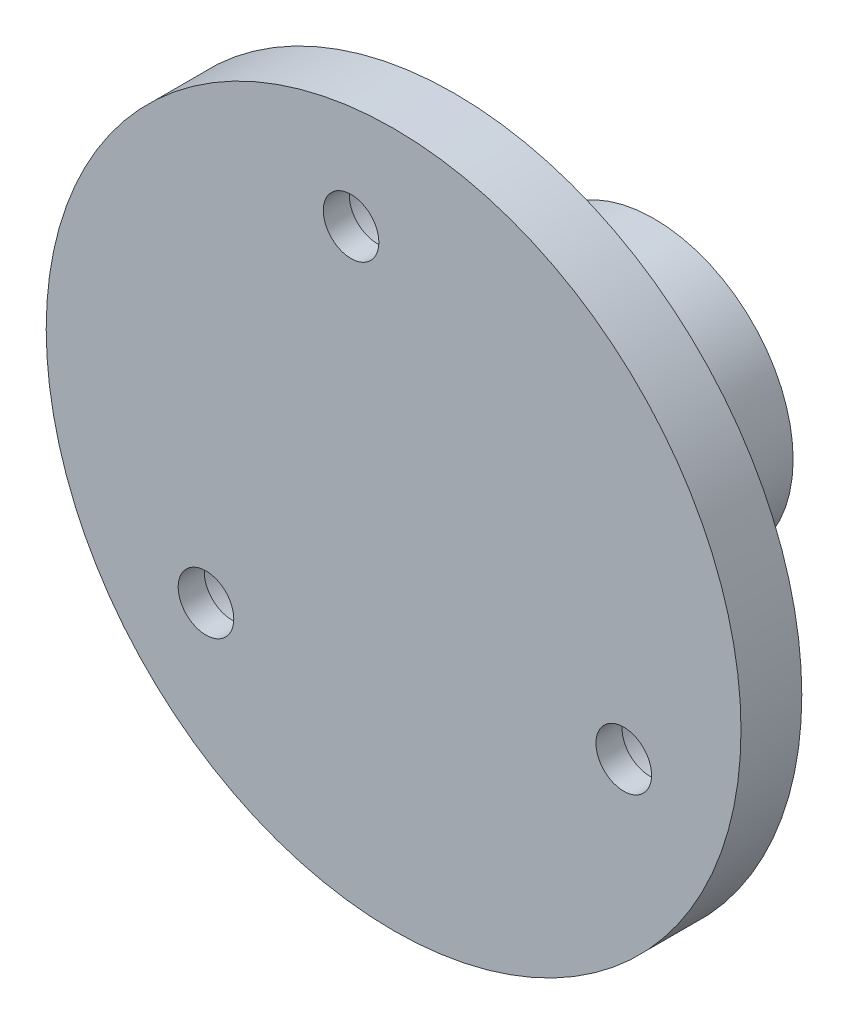
SolidWorks part; units mm, degrees
ref_plane "정면" through (0, 0, 0) normal (0, 0, 1) x (1, 0, 0)
ref_plane "윗면" through (0, 0, 0) normal (0, 1, 0) x (1, 0, 0)
ref_plane "우측면" through (0, 0, 0) normal (1, 0, 0) x (0, 0, -1)
sketch "Sketch1" plane through (0, 0, 0) normal (0, 0, 1) x (1, 0, 0)
  circle A0 centre (0, 0) radius 20
  dimension "D1" = 40
extrude "Boss-Extrude1" add sketch "Sketch1" along normal blind 3.5
sketch "Sketch5" plane through (0, 0, 3.5) normal (0, 0, 1) x (1, 0, 0)
  line L0 (0, 0) -> (-20, 0) construction
  line L1 (0, 0) -> (-10.8012, 9.0633) construction
  line L2 (0, 0) -> (-2.4484, 13.8858) construction
  line L3 (0, 0) -> (0, 15.3364) construction
  circle A0 centre (0, 0) radius 20 construction
  circle A2 centre (-2.4484, 13.8858) radius 1.6
  dimension "D5" = 3.2
  dimension "D1" = 40
  dimension "D2" = 14.1
  dimension "D4" = 40
extrude "Cut-Extrude3" cut sketch "Sketch5" against normal blind 15
sketch "Sketch6" plane through (0, 0, 0) normal (0, 1, 0) x (1, 0, 0)
  line L0 (0, -3.5) -> (0, 2.8067) construction
  line L1 (-20, -3.5) -> (20, -3.5) construction
pattern_circular "CirPattern1" count 3 over 360 about axis through (0, 0, 3.5) along (0, 0, -1) of "Cut-Extrude3" reverse direction yes
sketch "Sketch10" plane through (0, 0, 0) normal (0, 0, -1) x (-1, 0, 0)
  line L0 (0, 0) -> (0, 26.29) construction
  line L2 (-4.6399, 26.3144) -> (0, 0) construction
  circle A0 centre (-1.9101, 10.8329) radius 1.25
  circle A1 centre (-1.9101, 10.8329) radius 2.25
  dimension "D5" = 2.5
  dimension "D6" = 4.5
  dimension "D1" = 26.29
  dimension "D2" = 4.64
  dimension "D3" = 10
  dimension "D4" = 11
sketch "Sketch11" plane through (0, 0, 0) normal (0, 0, -1) x (-1, 0, 0)
  line L1 (3.1173, -2.5064) -> (1.9929, 3.4682)
  circle A0 centre (0, 0) radius 8
  arc A1 (1.9929, 3.4682) -> (3.1173, -2.5064) centre (0, 0) ccw
  dimension "D1" = 16
  dimension "D2" = 8
  dimension "D3" = 2.6
extrude "Boss-Extrude2" add sketch "Sketch11" along normal blind 11.5
ref_plane "Plane1" through (0, 0, 0) normal (0.9848, -0.1736, 0) x (0, 0, -1)
ref_plane "Plane2" through (0, 0, 0) normal (-0.1736, -0.9848, 0) x (0, 0, -1)
sketch "Sketch13" plane through (0, 0, 0) normal (0, 0, -1) x (-1, 0, 0)
  line L0 (-7.643, -2.3631) -> (7.9903, 0.3935)
  line L1 (-3.416, -0.6023) -> (3.416, 0.6023) construction
  arc A0 (-7.643, -2.3631) -> (7.9903, 0.3935) centre (0, 0) ccw
  circle A1 centre (0, 0) radius 8 construction
  dimension "D1" = 1
extrude "Cut-Extrude4" cut sketch "Sketch13" along normal blind 1.5
sketch "Sketch14" plane through (0, 0, 0) normal (0.9848, -0.1736, 0) x (0, 0, -1)
  line L0 (1.5, -1) -> (0, -1) construction
  line L1 (2, -1) -> (11.5, -1)
  line L2 (2, -1) -> (2, -24.9186)
  line L3 (2, -24.9186) -> (11.5, -24.9186)
  line L4 (11.5, -1) -> (11.5, -24.9186)
  line L5 (11.5, -8) -> (11.5, 8) construction
extrude "Cut-Extrude5" cut sketch "Sketch14" against normal blind 1 and the other way blind 1
sketch "Sketch15" plane through (-0.9848, 0.1736, 0) normal (0.9848, -0.1736, 0) x (0, 0, -1)
  line L0 (11.5, -7.9373) -> (11.5, 8) construction
  line L1 (1.5, -3.9762) -> (11.5, -3.9762)
  line L2 (1.5, -3.9762) -> (1.5, -12.4762)
  line L3 (1.5, -12.4762) -> (11.5, -12.4762)
  line L4 (11.5, -3.9762) -> (11.5, -12.4762)
  line L5 (1.5, -1) -> (1.5, -8) construction
  dimension "D1" = 8.5
extrude "Boss-Extrude3" add sketch "Sketch15" against normal blind 2.5
ref_plane "Plane3" through (0, 0, 0) normal (0.9848, -0.1736, 0) x (0, 0, -1)
mirror "Mirror1" about plane through (0, 0, 0) normal (0.9848, -0.1736, 0) of "Boss-Extrude3"
sketch "Sketch16" plane through (-3.4468, 0.6078, 0) normal (-0.9848, 0.1736, 0) x (0, 0, 1)
  line L0 (-1.5, -9.835) -> (-11.5, -9.835) construction
  line L1 (-1.5, -7.1937) -> (-1.5, -12.4762) construction
  line L2 (-11.5, -12.4762) -> (-11.5, -7.1937) construction
  circle A0 centre (-8.6, -9.835) radius 1.15
  circle A1 centre (-4.4, -9.835) radius 1.15
  dimension "D1" = 2.3
  dimension "D2" = 2.9
  dimension "D3" = 2.9
extrude "Cut-Extrude6" cut sketch "Sketch16" against normal through all both and the other way through all
sketch "Sketch17" plane through (0, 0, -11.5) normal (0, 0, -1) x (-1, 0, 0)
  line L0 (2.5551, 0.4809) -> (14.3802, 2.566) construction
  line L1 (4.2243, 4.8369) -> (5.6134, -3.0416)
  line L2 (5.6134, -3.0416) -> (11.0299, -2.0865)
  line L3 (11.0299, -2.0865) -> (9.6407, 5.792)
  line L4 (9.6407, 5.792) -> (4.2243, 4.8369)
  line L5 (3.1173, -2.5064) -> (1.9929, 3.4682) construction
  line L6 (-4.6399, 26.3144) -> (0, 0) construction
  point P11 (9.3497, 1.6836)
  dimension "D1" = 5.5
  dimension "D2" = 5
  dimension "D3" = 8
extrude "Boss-Extrude5" add sketch "Sketch17" against normal up to surface (10 mm away) up to face at (-1.2661, -6.8207, -1.5)
sketch "Sketch20" plane through (0, 0, -11.5) normal (0, 0, -1) x (-1, 0, 0)
  line L0 (6.2909, -1.1247) -> (5.5268, 3.2085)
  line L1 (6.2909, -1.1247) -> (8.6544, -0.7079)
  line L2 (5.5268, 3.2085) -> (7.8904, 3.6252)
  line L3 (8.6544, -0.7079) -> (7.8904, 3.6252)
  line L4 (0, 0) -> (14.2938, 2.5204) construction
  line L5 (-3.416, -0.6023) -> (3.416, 0.6023) construction
  line L6 (-4.6399, 26.3144) -> (0, 0) construction
  dimension "D1" = 4.4
  dimension "D2" = 2.4
  dimension "D3" = 6
extrude "Cut-Extrude7" cut sketch "Sketch20" against normal up to surface (10 mm away) up to face at (-2.9749, -4.8318, -1.5)
sketch "Sketch19" plane through (-10.3405, 1.8233, 0) normal (-0.9848, 0.1736, 0) x (0, 0, 1)
  line L0 (-11.5, 0.0299) -> (-1.5, 0) construction
  line L1 (-11.5, -3.9701) -> (-11.5, 4.0299) construction
  line L2 (-3.4687, 0) -> (3.4687, 0) construction
  line L4 (-1.5, -3.9701) -> (-1.5, 4.0299) construction
  circle A0 centre (-8.9, 0.0221) radius 1.15
  circle A1 centre (-4.7, 0.0096) radius 1.15
  dimension "D1" = 2.3
  dimension "D3" = 3.2
  dimension "D2" = 2.6
extrude "Cut-Extrude9" cut sketch "Sketch19" against normal blind 10
fillet "Fillet1" radius 3 1 edges at (1.3892, 7.8785, 0)
fillet "Fillet2" radius 2 2 edges at (-6.8537, 0.1931, 0) (7.1274, -2.2722, 0)
sketch "Sketch21" plane through (0, 0, 0) normal (0, 0, -1) x (-1, 0, 0)
  circle A0 centre (2.4484, 13.8858) radius 3
  circle A1 centre (10.8012, -9.0633) radius 3
  circle A2 centre (-13.2497, -4.8225) radius 3
  dimension "D1" = 6
extrude "Cut-Extrude10" cut sketch "Sketch21" against normal blind 2
